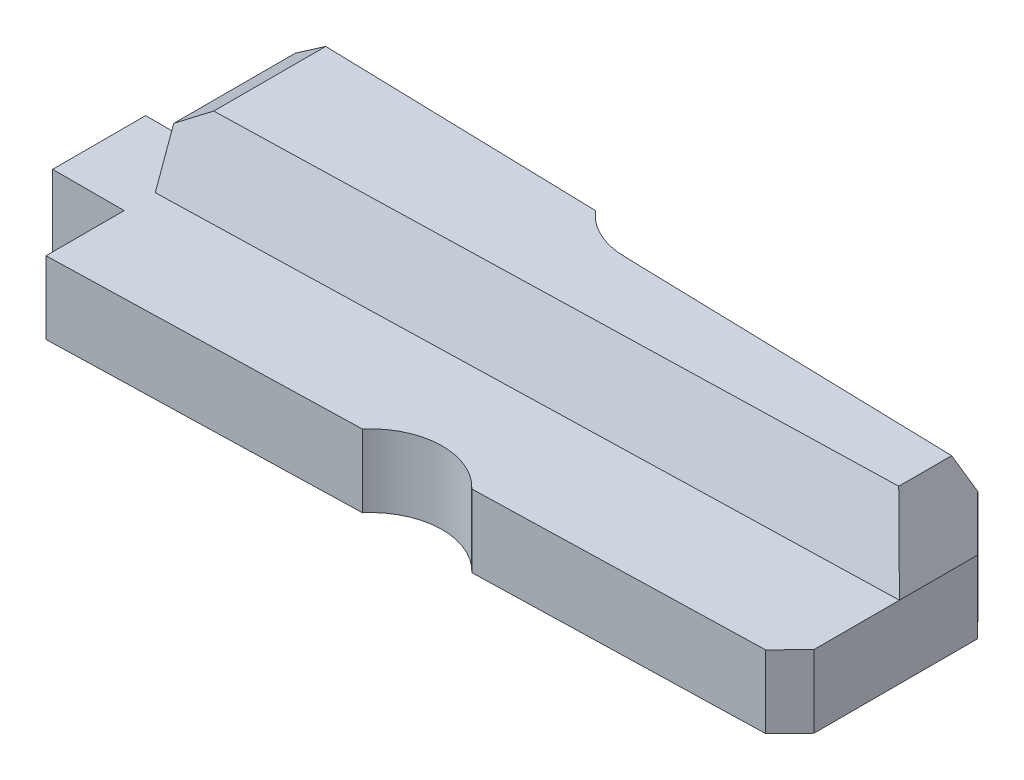
SolidWorks part; units mm, degrees
ref_plane "Front Plane" through (0, 0, 0) normal (0, 0, 1) x (1, 0, 0)
ref_plane "Top Plane" through (0, 0, 0) normal (0, 1, 0) x (1, 0, 0)
ref_plane "Right Plane" through (0, 0, 0) normal (1, 0, 0) x (0, 0, -1)
sketch "Sketch1" plane through (0, 0, 0) normal (0, 1, 0) x (1, 0, 0)
  line L0 (-14.914, 10.7961) -> (-14.914, -10.7339)
  line L1 (-14.914, -10.7339) -> (57.586, -8.8214)
  line L2 (57.586, -8.8214) -> (57.586, 8.8786)
  line L3 (57.586, 8.8786) -> (-14.914, 10.7961)
  dimension "D1" = 21.53
  dimension "D2" = 17.7
  dimension "D3" = 72.5
  dimension "D4" = 88.485
extrude "Boss-Extrude1" add sketch "Sketch1" along normal blind 6.08
sketch "Sketch2" plane through (0, 6.08, 0) normal (0, 1, 0) x (1, 0, 0)
  line L2 (-13.064, 10.7961) -> (-13.064, -10.7339)
  line L3 (-13.064, 10.7472) -> (-13.064, -1.5219)
  line L5 (-15.1556, -1.5771) -> (57.3444, 0.3354)
  line L6 (-13.064, -1.5219) -> (57.586, 0.3418)
  line L8 (57.586, 8.8786) -> (-14.914, 10.7961)
  line L9 (57.586, 8.8786) -> (-13.064, 10.7472)
  line L11 (57.586, -8.8214) -> (57.586, 8.8786)
  line L12 (57.586, 0.3418) -> (57.586, 8.8786)
  dimension "D1" = 1.85
  dimension "D2" = 9.16
  dimension "D3" = 0
  dimension "D4" = 0
extrude "Boss-Extrude2" add sketch "Sketch2" along normal blind 6.09
ref_plane "Plane1" through (0.0789, 1.0895, 2.9922) normal (0.0248, 0.342, 0.9394) x (0.9997, 0, -0.0264)
ref_axis "Axis1" through (-13.064, 12.17, -0.6954) along (0.9997, 0, -0.0264)
sketch "Sketch4" plane through (0.0789, 1.0895, 2.9922) normal (0.0248, 0.342, 0.9394) x (0.9997, 0, -0.0264)
  line L2 (-13.0996, 5.3108) -> (57.5749, 5.3108)
  line L3 (-13.0996, 5.3108) -> (57.8001, 5.3108)
  line L5 (-13.0996, 11.0335) -> (-13.0996, 5.3108)
  line L6 (-13.0996, 14.6247) -> (-13.0996, 5.3108)
  line L7 (-13.0996, 14.6247) -> (57.8001, 14.6247)
  line L10 (57.8001, 13.9523) -> (57.8001, 2.5162) construction
  line L11 (57.8001, 13.9523) -> (57.8001, 2.5162)
  line L12 (57.8001, 14.6247) -> (57.8001, 5.3108)
  dimension "D1" = 0
  dimension "D2" = 0
  dimension "D3" = 0
extrude "Cut-Extrude4" cut sketch "Sketch4" along normal blind 13.09 contours L3 L12 L7 L6
ref_plane "Plane2" through (52.8037, 19.219, 0) normal (0.9397, 0.342, 0) x (0, 0, -1)
sketch "Sketch5" plane through (52.8037, 19.219, 0) normal (0.9397, 0.342, 0) x (0, 0, -1)
  line L1 (-14.2418, -13.9822) -> (-14.2418, -1.7479)
  line L2 (-8.8214, -13.9822) -> (0.3418, -13.9822)
  line L3 (-14.2418, -13.9822) -> (15.0642, -13.9822)
  line L4 (-14.2418, -1.7479) -> (15.0642, -1.7479)
  line L5 (15.0642, -1.7479) -> (15.0642, -13.9822)
  dimension "D1" = 0
extrude "Cut-Extrude5" cut sketch "Sketch5" along normal blind 19.09
sketch "Sketch6" plane through (0, 0, 0) normal (0, -1, 0) x (1, 0, 0)
  line L0 (-14.914, 10.7339) -> (-14.914, 8.7339)
  line L1 (-14.914, -10.7961) -> (-14.914, 10.7339) construction
  line L2 (-14.914, 8.7339) -> (-12.914, 10.6811)
  line L3 (-14.914, 10.7339) -> (57.586, 8.8214) construction
  line L4 (-12.914, 10.6811) -> (-14.914, 10.7339)
  line L5 (-14.914, -10.7961) -> (-12.914, -10.7432)
  line L6 (57.586, -8.8786) -> (-14.914, -10.7961) construction
  line L7 (-12.914, -10.7432) -> (-14.914, -8.7961)
  line L8 (-14.914, -8.7961) -> (-14.914, -10.7961)
  line L9 (55.5866, 8.8741) -> (57.586, 8.8214)
  line L10 (57.586, 8.8214) -> (57.586, 6.8214)
  line L11 (57.586, 8.8214) -> (57.586, -8.8786) construction
  line L12 (57.586, 6.8214) -> (55.5866, 8.8741)
  line L13 (57.586, -8.8786) -> (57.586, -6.8786)
  line L14 (57.586, -6.8786) -> (55.586, -8.9315)
  line L15 (55.586, -8.9315) -> (57.586, -8.8786)
  line L16 (27.216, 19.304) -> (27.216, -14.3897) construction
  circle A1 centre (27.216, 13.6239) radius 6
  circle A2 centre (27.216, -13.6832) radius 6
  dimension "D11" = 12
  dimension "D12" = 12
  dimension "D1" = 2
  dimension "D2" = 2
  dimension "D3" = 2
  dimension "D4" = 2
  dimension "D5" = 2
  dimension "D6" = 2
  dimension "D7" = 2
  dimension "D8" = 2
  dimension "D9" = 42.13
  dimension "D10" = 4
  dimension "D13" = 4
extrude "Cut-Extrude6" cut sketch "Sketch6" against normal through all
ref_plane "Plane3" through (0, 7.78, 0) normal (0, 1, 0) x (1, 0, 0)
ref_axis "Axis2" through (360.074, 7.78, -0.8784) along (-0.9997, 0, -0.0264)
ref_plane "Plane4" through (0.3053, 5.2601, -11.542) normal (0.0241, 0.4146, -0.9097) x (-0.9997, 0.01, -0.0219)
sketch "Sketch7" plane through (0.3053, 5.2601, -11.542) normal (0.0241, 0.4146, -0.9097) x (-0.9997, 0.01, -0.0219)
  line L0 (-26.9217, 7.8879) -> (-26.9217, 3.0644)
  line L1 (-359.8729, 6.7147) -> (-60.2731, 3.43) construction
  line L2 (-26.9217, 3.0644) -> (-63.5754, 3.4662)
  line L3 (-63.5754, 3.4662) -> (-63.5754, 10.3897)
  line L4 (-63.5754, 10.3897) -> (-26.9217, 9.9878)
  line L5 (-26.9217, 9.9878) -> (-26.9217, 7.8879)
  ellipse E0 centre (-26.7871, 5.3996) end of major axis (-20.7874, 5.3339) minor radius 2.4875 (-22.297, 7.0089) -> (-31.2408, 7.1069) ccw construction
extrude "Cut-Extrude7" cut sketch "Sketch7" along normal blind 11.09
ref_plane "Cut surface" through (-3.214, 0, 0) normal (-1, 0, 0) x (0, 0, 1)
sketch "Sketch10" plane through (-3.214, 0, 0) normal (-1, 0, 0) x (0, 0, 1)
  line L1 (-17.6293, 15.2246) -> (18.4681, 15.2246)
  line L2 (-17.6293, 15.2246) -> (-17.6293, -7.7626)
  line L3 (-17.6293, -7.7626) -> (18.4681, -7.7626)
  line L4 (18.4681, 15.2246) -> (18.4681, -7.7626)
extrude "Cut-Extrude11" cut sketch "Sketch10" along normal through all
sketch "Sketch12" plane through (-3.214, 0, 0) normal (-1, 0, 0) x (0, 0, 1)
  line L1 (-3.9307, 6.08) -> (3.8693, 6.08)
  line L2 (-3.9307, 6.08) -> (-3.9307, 0)
  line L3 (-3.9307, 0) -> (3.8693, 0)
  line L4 (3.8693, 6.08) -> (3.8693, 0)
  line L5 (-10.4867, 0) -> (10.4253, 0) construction
  line L6 (-0.0307, -3.669) -> (-0.0307, 11.8159) construction
  line L8 (1.2621, 6.08) -> (10.4253, 6.08) construction
  line L11 (-10.4867, 12.17) -> (-10.4867, 0) construction
  line L12 (10.4253, 0) -> (10.4253, 6.08) construction
  dimension "D1" = 7.8
  dimension "D4" = 0
extrude "Boss-Extrude4" add sketch "Sketch12" along normal blind 6
ref_plane "Plane5" through (-6.7754, 9.6763, 0) normal (-0.5736, 0.8192, 0) x (0, 0, 1)
ref_plane "Plane6" through (-5.9151, 8.4476, 0) normal (-0.5736, 0.8192, 0) x (0, 0, 1)
sketch "Sketch13" plane through (-5.9151, 8.4476, 0) normal (-0.5736, 0.8192, 0) x (0, 0, 1)
  line L1 (-13.6641, 9.5503) -> (5.0822, 9.5503)
  line L2 (-13.6641, 9.5503) -> (-13.6641, 0.4074)
  line L3 (-13.6641, 0.4074) -> (5.0822, 0.4074)
  line L4 (5.0822, 9.5503) -> (5.0822, 0.4074)
extrude "Cut-Extrude12" cut sketch "Sketch13" along normal up to next
